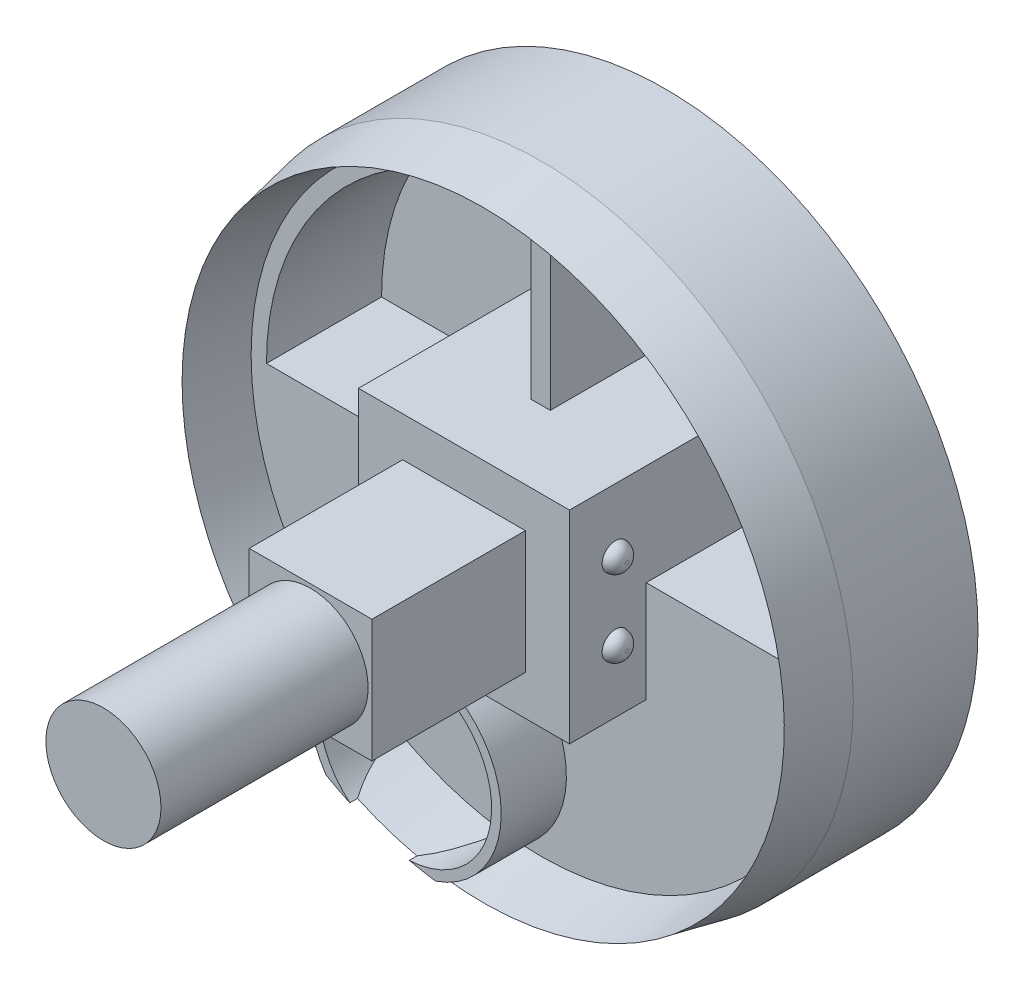
SolidWorks part; units mm, degrees
ref_plane "Front Plane" through (0, 0, 0) normal (0, 0, 1) x (1, 0, 0)
ref_plane "Top Plane" through (0, 0, 0) normal (0, 1, 0) x (1, 0, 0)
ref_plane "Right Plane" through (0, 0, 0) normal (1, 0, 0) x (0, 0, -1)
sketch "Sketch1" plane through (0, 0, 0) normal (0, 0, 1) x (1, 0, 0)
  line L0 (34.925, 0) -> (97.155, 0) construction
  line L1 (-34.925, -33.528) -> (34.925, -33.528)
  line L2 (-34.925, -33.528) -> (-34.925, 33.528)
  line L3 (-34.925, 33.528) -> (34.925, 33.528)
  line L4 (34.925, -33.528) -> (34.925, 33.528)
  line L5 (-34.925, -33.528) -> (34.925, 33.528) construction
  line L6 (-34.925, 33.528) -> (34.925, -33.528) construction
  line L7 (-34.925, 0) -> (-97.155, 0) construction
  line L8 (0, 33.528) -> (0, 90.805) construction
  line L9 (0, 0) -> (34.925, 0) construction
  line L10 (-23.241, -68.707) -> (-23.241, -33.528) construction
  line L11 (-23.241, -36.957) -> (-23.241, -33.528)
  circle A0 centre (0, 0) radius 97.155 construction
  circle A1 centre (0, 0) radius 90.805 construction
  circle A2 centre (-23.241, -68.707) radius 31.75 construction
  circle A3 centre (0, 0) radius 103.505 construction
  point P0 (0, 0)
  dimension "D6" = 181.61
  dimension "D7" = 63.5
  dimension "D1" = 69.85
  dimension "D2" = 67.056
  dimension "D3" = 62.23
  dimension "D4" = 62.23
  dimension "D5" = 34.925
  dimension "D8" = 11.684
  dimension "D9" = 3.429
  dimension "D10" = 12.7
sketch "Sketch2" plane through (0, 0, 0) normal (0, 0, 1) x (1, 0, 0)
  line L0 (-34.925, 0) -> (-97.155, 0) construction
  line L1 (-90.805, 0) -> (-34.925, 0)
  line L2 (34.925, 0) -> (90.805, 0)
  line L3 (34.925, 0) -> (97.155, 0) construction
  line L4 (34.925, 0) -> (34.925, -33.528)
  line L5 (34.925, -33.528) -> (-34.925, -33.528)
  line L6 (-34.925, -33.528) -> (-34.925, 0)
  arc A0 (90.805, 0) -> (-90.805, 0) centre (0, 0) cw
  circle A1 centre (0, 0) radius 90.805 construction
  point P11 (-90.805, 0)
  point P15 (0, 0)
  point P20 (0, 0)
  point P21 (0, 0)
extrude "Boss-Extrude1" add sketch "Sketch2" along normal blind 6.35
extrude "Boss-Extrude2" add sketch "Sketch1" along normal blind 31.75 contours L3 L4 L1 L2
ref_plane "Plane1" through (0, 0, -31.75) normal (0, 0, 1) x (1, 0, 0)
sketch "Sketch3" plane through (0, 0, -31.75) normal (0, 0, 1) x (1, 0, 0)
  circle A0 centre (0, 0) radius 103.505
  circle A1 centre (0, 0) radius 90.805
  circle A2 centre (0, 0) radius 90.805 construction
  circle A3 centre (0, 0) radius 103.505 construction
extrude "Boss-Extrude3" add sketch "Sketch3" along normal up to surface (38.1 mm away) up to face at (0, -26.3102, 6.35)
extrude "Boss-Extrude4" add sketch "Sketch3<2>" against normal blind 3.175 contours A0
sketch "Sketch3<2>" plane through (0, 0, -31.75) normal (0, 0, 1) x (1, 0, 0) same geometry as "Sketch3"
sketch "Sketch5" plane through (0, 0, 6.35) normal (0, 0, 1) x (1, 0, 0)
  line L0 (-90.805, 0) -> (-34.925, 0)
  line L1 (-34.925, 0) -> (-34.925, -6.35)
  line L2 (-34.925, -33.528) -> (-34.925, 33.528) construction
  line L3 (-34.925, -6.35) -> (-90.5827, -6.35)
  line L4 (34.925, 0) -> (90.805, 0)
  line L5 (34.925, -6.35) -> (90.5827, -6.35)
  line L6 (34.925, -33.528) -> (34.925, 33.528) construction
  line L7 (34.925, 0) -> (34.925, -6.35)
  line L14 (-34.925, 33.528) -> (34.925, -33.528) construction
  line L16 (0, 33.528) -> (3.175, 33.528)
  line L17 (-34.925, 33.528) -> (34.925, 33.528) construction
  line L18 (0, 33.528) -> (-3.175, 33.528)
  line L19 (3.175, 33.528) -> (3.175, 94.488)
  line L20 (3.175, 94.488) -> (-3.175, 94.488)
  line L21 (-3.175, 94.488) -> (-3.175, 33.528)
  circle A0 centre (0, 0) radius 90.805 construction
  arc A2 (90.805, 0) -> (90.5827, -6.35) centre (0, 0) cw
  arc A3 (-90.805, 0) -> (-90.5827, -6.35) centre (0, 0) ccw
  dimension "D1" = 6.35
  dimension "D2" = 6.35
  dimension "D3" = 6.35
  dimension "D4" = 60.96
extrude "Boss-Extrude5" add sketch "Sketch5" against normal up to surface (38.1 mm away) up to face at (90.805, 0, -31.75)
extrude "Boss-Extrude6" add sketch "Sketch1<3>" against normal up to surface (31.75 mm away) contours L2 L3 L4 L1 up to face at (0, 14.5086, -31.75)
sketch "Sketch1<3>" plane through (0, 0, 0) normal (0, 0, 1) x (1, 0, 0) same geometry as "Sketch1"
sketch "Sketch6" plane through (0, 0, 0) normal (0, 1, 0) x (1, 0, 0)
  line L0 (-103.505, -6.35) -> (-99.695, -25.4)
  line L1 (-103.505, -6.35) -> (103.505, -6.35) construction
  line L2 (-99.695, -25.4) -> (-95.885, -6.35)
  line L3 (-95.885, -6.35) -> (-103.505, -6.35)
  line L4 (-99.695, -6.35) -> (-99.695, -25.4) construction
  line L5 (0, 0) -> (0, -31.75) construction
  line L6 (-34.925, -31.75) -> (34.925, -31.75) construction
  dimension "D1" = 7.62
  dimension "D2" = 19.05
revolve "Revolve1" add sketch "Sketch6" angle 360 about L5
sketch "Sketch7" plane through (0, 0, 6.35) normal (0, 0, 1) x (1, 0, 0)
  arc A0 (-13.1782, -98.8202) -> (-49.518, -86.5278) centre (-23.241, -68.707) ccw
  arc A1 (-21.9344, -97.2521) -> (-41.608, -90.5973) centre (-23.241, -68.707) ccw
  circle A2 centre (-23.241, -68.707) radius 31.75 construction
  arc A3 (-49.518, -86.5278) -> (-41.608, -90.5973) centre (0, 0) ccw
  arc A5 (-21.9344, -97.2521) -> (-13.1782, -98.8202) centre (0, 0) ccw
  dimension "D1" = 3.175
  dimension "D2" = 99.695
extrude "Boss-Extrude7" add sketch "Sketch7" along normal blind 21.59
sketch "Sketch8" plane through (34.925, 0, 0) normal (1, 0, 0) x (0, 0, -1)
  line L0 (-16.51, -12.7) -> (-16.51, 12.7) construction
  line L1 (-16.51, 0) -> (-31.75, 0) construction
  line L2 (-31.75, -33.528) -> (-31.75, 33.528) construction
  circle A0 centre (-16.51, 12.7) radius 4.445
  circle A1 centre (-16.51, -12.7) radius 4.445
  dimension "D2" = 8.89
  dimension "D3" = 8.89
  dimension "D1" = 25.4
  dimension "D4" = 15.24
extrude "Boss-Extrude8" add sketch "Sketch8" along normal blind 3.81
fillet "Fillet1" radius 3.81 2 edges at (38.735, 12.7, 12.065) (38.735, -12.7, 12.065)
ref_plane "Plane2" through (0, 0, 0) normal (1, 0, 0) x (0, 0, -1)
mirror "Mirror3" about plane through (0, 0, 0) normal (1, 0, 0) of "Fillet1", "Boss-Extrude8"
sketch "Sketch9" plane through (0, 0, 31.75) normal (0, 0, 1) x (1, 0, 0)
  line L1 (-20.32, -20.32) -> (20.32, -20.32)
  line L2 (-20.32, -20.32) -> (-20.32, 20.32)
  line L3 (-20.32, 20.32) -> (20.32, 20.32)
  line L4 (20.32, -20.32) -> (20.32, 20.32)
  line L5 (-20.32, -20.32) -> (20.32, 20.32) construction
  line L6 (-20.32, 20.32) -> (20.32, -20.32) construction
  point P0 (0, 0)
  point P5 (0, 0)
  dimension "D1" = 40.64
  dimension "D2" = 40.64
extrude "Boss-Extrude9" add sketch "Sketch9" along normal blind 50.8
sketch "Sketch10" plane through (0, 0, 82.55) normal (0, 0, 1) x (1, 0, 0)
  circle A0 centre (0, 0) radius 19.05
  point P3 (0, 0)
  dimension "D1" = 38.1
extrude "Boss-Extrude10" add sketch "Sketch10" along normal blind 68.58
equation "\"D6@Sketch1\"=2*(\"D5@Sketch1\"+2.2)"
